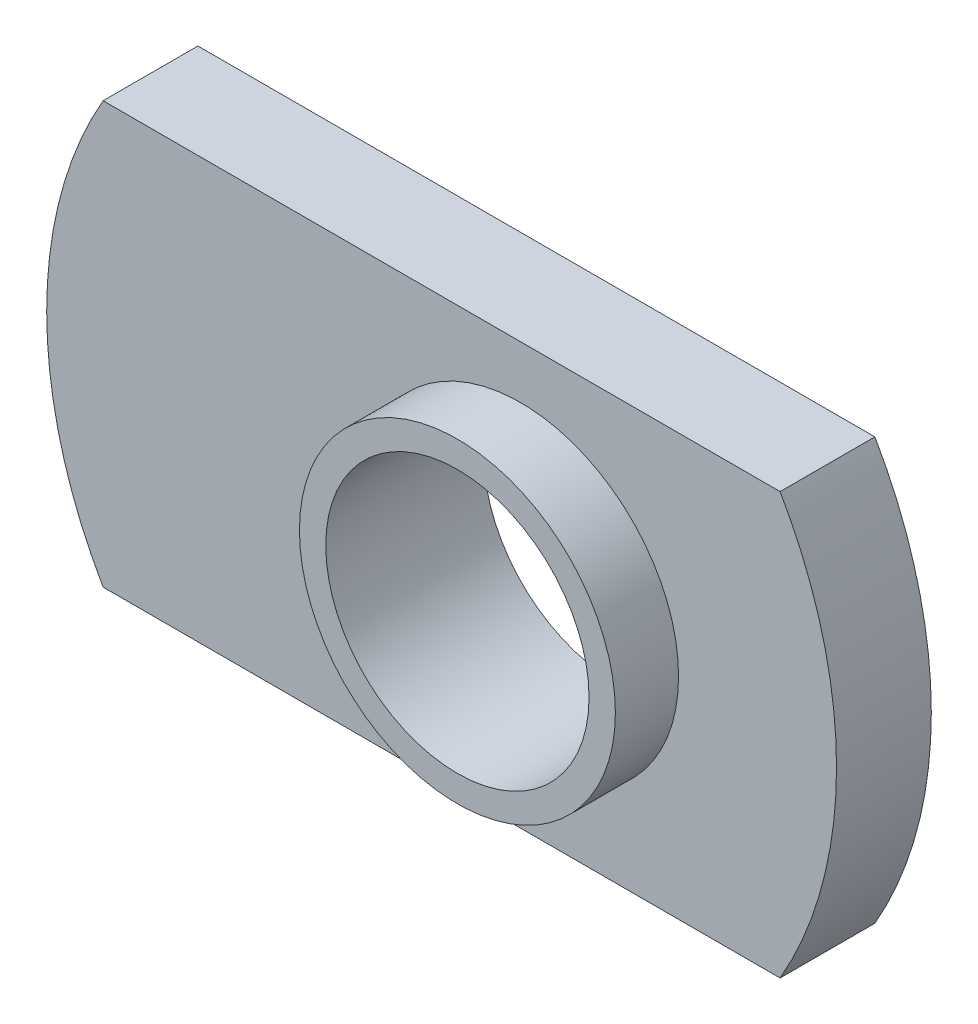
SolidWorks part; units mm, degrees
ref_plane "Front Plane" through (0, 0, 0) normal (0, 0, 1) x (1, 0, 0)
ref_plane "Top Plane" through (0, 0, 0) normal (0, 1, 0) x (1, 0, 0)
ref_plane "Right Plane" through (0, 0, 0) normal (1, 0, 0) x (0, 0, -1)
sketch "Sketch7" plane through (0, 0, 0) normal (0, 0, 1) x (1, 0, 0)
  line L0 (-7.9282, 4) -> (4.9282, 4)
  line L1 (-9, 0) -> (6, 0) construction
  line L2 (0, 0) -> (1.7678, -1.7678) construction
  line L3 (-7.9282, -4) -> (4.9282, -4)
  circle A0 centre (0, 0) radius 2.5 construction
  arc A1 (4.9282, -4) -> (4.9282, 4) centre (-2, 0) ccw
  arc A5 (-7.9282, -4) -> (-7.9282, 4) centre (-1, 0) cw
  circle A6 centre (0, 0) radius 3 construction
  point P8 (1.7678, -1.7678)
  dimension "D1" = 45
  dimension "Thread Dia" = 5
  dimension "Nut Width" = 6
  dimension "Side Radius" = 8
  dimension "Length" = 15
  dimension "Offset" = 6
  dimension "Width" = 8
extrude "Boss-Extrude1" add sketch "Sketch7" along normal mid plane 1.8 separate body
sketch "Sketch8" plane through (0, 0, 0.9) normal (0, 0, 1) x (1, 0, 0)
  circle A2 centre (0, 0) radius 2.5 construction
  circle A3 centre (0, 0) radius 2.5
  circle A4 centre (0, 0) radius 3 construction
  circle A5 centre (0, 0) radius 3
extrude "Boss-Extrude2" add sketch "Sketch8" along normal blind 1.2
sketch "Sketch1" plane through (0, 0, 0) normal (0, 0, 1) x (1, 0, 0)
  circle A0 centre (0, 0) radius 2.5
  circle A3 centre (0, 0) radius 2.5 construction
extrude "Cut-Extrude1" cut sketch "Sketch1" against normal through all both and the other way through all
sketch "Sketch6" plane through (0, 0, -0.9) normal (0, 0, -1) x (-1, 0, 0)
  line L0 (-6, 4) -> (-6, -4) construction
  line L1 (-6, 4) -> (9, 4) construction
  line L2 (-6, -4) -> (9, -4) construction
  line L3 (9, 4) -> (9, -4) construction
  line L6 (7.9282, -4) -> (-4.9282, -4) construction
  line L7 (7.9282, 4) -> (-4.9282, 4) construction
  arc A2 (7.9282, -4) -> (7.9282, 4) centre (1, 0) ccw construction
  arc A3 (-4.9282, 4) -> (-4.9282, -4) centre (2, 0) ccw construction
sketch "Sketch2" plane through (0, 0, -0.9) normal (0, 0, -1) x (-1, 0, 0)
  circle A2 centre (0, 0) radius 2.5
  circle A3 centre (0, 0) radius 2.5
  dimension "D1" = 0
sketch "Sketch3" plane through (0, 0, 0) normal (1, 0, 0) x (0, 0, -1)
  line L0 (0.85, 2.5866) -> (1.65, 2.5866) construction
  line L1 (1.65, 2.5866) -> (1.25, 1.8938) construction
  line L2 (1.25, 1.8938) -> (0.85, 2.5866) construction
  line L3 (0.875, 2.5433) -> (1.625, 2.5433) construction
  line L5 (0.9, 2.5) -> (1.6, 2.5) construction
  line L7 (1.2, 1.9804) -> (1.3, 1.9804) construction
  line L8 (0.875, 2.5433) -> (1.625, 2.5433)
  line L9 (1.625, 2.5433) -> (1.3, 1.9804)
  line L10 (1.25, 1.9804) -> (1.25, 1.8938) construction
  line L11 (1.25, 2.5866) -> (1.25, 2.5) construction
  line L12 (1.3, 1.9804) -> (1.2, 1.9804)
  line L13 (1.2, 1.9804) -> (0.875, 2.5433)
  point P9 (1.25, 2.5433)
  dimension "D2" = 0.1
curve "Helix/Spiral1" pitch 0.8 height 3.8 turns 4.75
sweep "Sweep1" [suppressed] add profiles "Sketch3" path "Helix/Spiral1"
split "Split1" [suppressed] bodies to split 106
sketch "Sketch4" [suppressed] plane through (0, 0, -0.9) normal (0, 0, -1) x (-1, 0, 0)
  circle A1 centre (0, 0) radius 2.5
  circle A2 centre (0, 0) radius 2.5
  dimension "D1" = 0
extrude "Cut-Extrude2" [suppressed] cut sketch "Sketch4" against normal through all draft 45
sketch "Sketch5" [suppressed] plane through (0, 0, 2.1) normal (0, 0, 1) x (1, 0, 0)
  circle A1 centre (0, 0) radius 2.5
  circle A2 centre (0, 0) radius 2.5
  dimension "D1" = 0
extrude "Cut-Extrude3" [suppressed] cut sketch "Sketch5" against normal through all draft 45
ref_plane "Contact Plane 1" through (0, 0, -0.9) normal (0, 0, -1) x (-1, 0, 0)
ref_axis "Center Axis 1" through (0, 0, 2.5981) along (0, 0, -1)
ref_plane "Plane1" through (6, 0, 0) normal (1, 0, 0) x (0, 0, -1)
equation "\"D2@Sketch3\" = \"Pitch@Sketch3\" / 8"
equation "\"D4@Helix/Spiral1\"=\"Pitch@Sketch3\""
equation "\"D3@Helix/Spiral1\" = \"Nut Thickness@Boss-Extrude1\" + \"Thread Depth@Boss-Extrude2\" + \"Pitch@Sketch3\""
